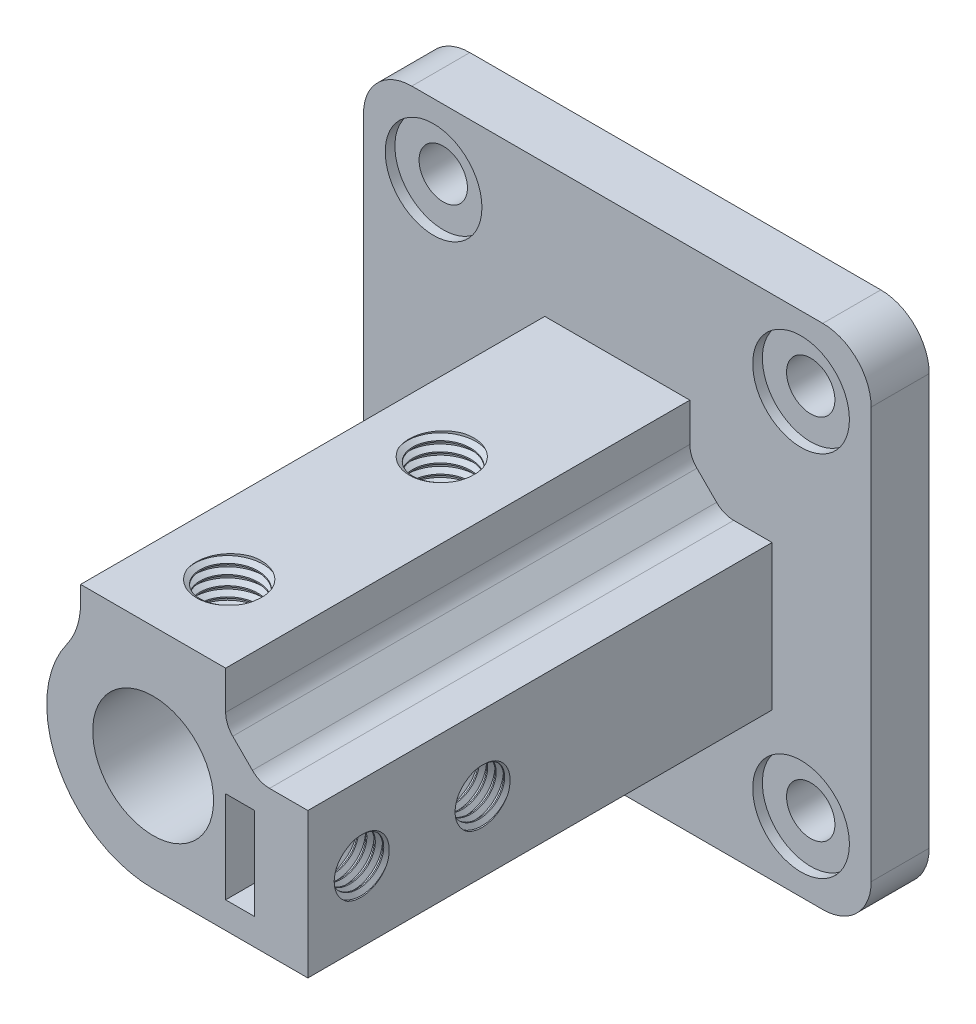
SolidWorks part; units mm, degrees
note: The reader was unsure of these and kept them because the rebuilt part matched: shared geometry of "Sketch1<4>", "Sketch1<5>".
ref_plane "Front Plane" through (0, 0, 0) normal (0, 0, 1) x (1, 0, 0)
ref_plane "Top Plane" through (0, 0, 0) normal (0, 1, 0) x (1, 0, 0)
ref_plane "Right Plane" through (0, 0, 0) normal (1, 0, 0) x (0, 0, -1)
sketch "Sketch1" plane through (0, 0, 0) normal (0, 0, 1) x (1, 0, 0)
  line L0 (0, 0) -> (-131291.8989, 0) construction
  line L1 (0, 0) -> (0, -131291.8989) construction
  line L2 (-15, 25) -> (15, 25)
  line L3 (0, -22) -> (32, -22)
  line L4 (-15, 25) -> (-15, 21.6564)
  line L5 (15, 25) -> (15, 17.0711)
  line L6 (32, -22) -> (32, 8)
  line L8 (24.0711, 8) -> (32, 8)
  line L9 (32, -7) -> (8.3062, -7) construction
  line L10 (-42.5, 52.5) -> (42.5, 52.5)
  line L11 (-52.5, 42.5) -> (-52.5, -42.5)
  line L12 (-42.5, -52.5) -> (42.5, -52.5)
  line L13 (52.5, 42.5) -> (52.5, -42.5)
  line L14 (0, -52.5) -> (0, 52.5) construction
  line L15 (-52.5, 0) -> (52.5, 0) construction
  line L16 (20.5355, 9.4645) -> (16.4645, 13.5355)
  line L17 (15, 2.5) -> (21, 2.5)
  line L18 (15, 2.5) -> (15, -16.5)
  line L19 (15, -16.5) -> (21, -16.5)
  line L20 (21, 2.5) -> (21, -16.5)
  line L21 (18, -16.5) -> (18, 2.5) construction
  line L22 (15, -7) -> (21, -7) construction
  arc A0 (-17.8378, 12.8768) -> (0, -22) centre (0, 0) ccw
  arc A2 (-17.8378, 12.8768) -> (-15, 21.6564) centre (-30, 21.6564) ccw
  arc A3 (-52.5, -42.5) -> (-42.5, -52.5) centre (-42.5, -42.5) ccw
  arc A4 (42.5, -52.5) -> (52.5, -42.5) centre (42.5, -42.5) ccw
  arc A5 (42.5, 52.5) -> (52.5, 42.5) centre (42.5, 42.5) cw
  arc A6 (-42.5, 52.5) -> (-52.5, 42.5) centre (-42.5, 42.5) ccw
  arc A7 (20.5355, 9.4645) -> (24.0711, 8) centre (24.0711, 13) ccw
  arc A8 (16.4645, 13.5355) -> (15, 17.0711) centre (20, 17.0711) cw
  point P10 (0, 25)
  point P21 (-52.5, -52.5)
  point P24 (52.5, -52.5)
  point P34 (18, -7)
  point P41 (22, 8)
  dimension "D1" = 44
  dimension "D6" = 15
  dimension "D8" = 10
  dimension "D14" = 5
  dimension "D2" = 30
  dimension "D3" = 30
  dimension "D4" = 25
  dimension "D5" = 32
  dimension "D7" = 105
  dimension "D9" = 19
  dimension "D10" = 6
  dimension "D11" = 11
  dimension "D12" = 135
  dimension "D13" = 10
extrude "Boss-Extrude1" add sketch "Sketch1" along normal blind 12 contours L10 A6 L11 A3 L12 A4 L13 A5 A0 A2 L4 L2 L5 L8 L6 L3 | A2 A0 L3 L6 L8 L5 L2 L4 L17 L20 L19 L18 | L20 L17 L18 L19
extrude "Boss-Extrude2" add sketch "Sketch1<4>" along normal blind 108 contours A0 L3 L6 L8 A7 L16 A8 L5 L2 L4 A2
sketch "Sketch1<4>" plane through (0, 0, 0) normal (0, 0, 1) x (1, 0, 0) same geometry as "Sketch1"
extrude "Cut-Extrude1" cut sketch "Sketch1<5>" against normal blind 48 from surface at 108 contours L20 L19 L18 L17 starting at face at (8.7964, 8.2207, 108)
sketch "Sketch1<5>" plane through (0, 0, 0) normal (0, 0, 1) x (1, 0, 0) same geometry as "Sketch1"
hole_wizard "Ø25.0mm Dowel Hole1" positions "3DSketch1" profile "Sketch2" hole size "Ø25.0" standard "ANSI Metric"
sketch3d "3DSketch1"
  line L0 (0, 0, 108) -> (0, 0, 12) construction
  point P0 (0, 0, 108)
sketch "Sketch2" plane through (0, 0, 108) normal (1, 0, 0) x (0, -1, 0)
  line L0 (0, 0) -> (0, 82)
  line L1 (0, 82) -> (12.5, 74.4892)
  line L2 (12.5, 74.4892) -> (12.5, 0)
  line L5 (12.5, 0) -> (0, 0)
  line L10 (0, 82) -> (-12.5, 74.4892) construction
  line L11 (0, -6.35) -> (0, 107.95) construction
  dimension "Hole Dia." = 25
  dimension "Hole Depth" = 82
  dimension "Drill Angle" = 118
hole_wizard "CBORE for M5 Hex Head Bolt1" positions "3DSketch3" profile "Sketch4" counterbore size "M5" standard "ANSI Metric" end condition through all
sketch3d "3DSketch3"
  line L0 (-52.5, 42.5, 12) -> (-52.5, -42.5, 12) construction
  line L1 (-42.5, 52.5, 12) -> (42.5, 52.5, 12) construction
  point P0 (38, 38.0257, 12)
  point P2 (-38, 38, 12)
  dimension "D1" = 76
  dimension "D2" = 14.5
  dimension "D3" = 14.5
sketch "Sketch4" plane through (38, 38.0257, 12) normal (1, 0, 0) x (0, -1, 0)
  line L0 (0, 0) -> (0, 12)
  line L1 (0, 12) -> (5, 12)
  line L3 (5, 12) -> (5, 2)
  line L4 (5, 2) -> (10, 2)
  line L5 (10, 2) -> (10, 0)
  line L7 (10, 0) -> (0, 0)
  line L11 (0, -6.35) -> (0, 107.95) construction
  dimension "Thru Hole Dia." = 10
  dimension "Thru Hole Depth" = 12
  dimension "C'Bore Dia." = 20
  dimension "C'Bore Depth" = 2
mirror "Mirror1" about plane through (0, 0, 0) normal (0, 1, 0) of "CBORE for M5 Hex Head Bolt1"
hole_wizard "M12x1.75 Tapped Hole1" positions "3DSketch6" profile "Sketch6" tap size "M12x1.75" standard "ANSI Metric"
sketch3d "3DSketch6"
  line L0 (32, -22, 108) -> (32, -22, 12) construction
  line L1 (32, -22, 108) -> (32, 8, 108) construction
  point P0 (32, -7, 97)
  point P2 (32, -7, 72)
  point P5 (0, 0, 0)
  dimension "D1" = 25
  dimension "D2" = 15
  dimension "D3" = 11
sketch "Sketch6" plane through (32, -7, 97) normal (0, 1, 0) x (0, 0, -1)
  line L0 (0, 0) -> (0, 14.0644)
  line L1 (0, 14.0644) -> (5.1, 11)
  line L2 (5.1, 11) -> (5.1, 0)
  line L5 (5.1, 0) -> (0, 0)
  line L10 (0, 14.0644) -> (-5.1, 11) construction
  line L11 (0, -6.35) -> (0, 107.95) construction
  dimension "Tap Drill Dia." = 10.2
  dimension "Tap Drill Depth" = 11
  dimension "Drill Angle" = 118
cosmetic thread "Hole Thread1" parameters "D1"=24, "D2"=12
cosmetic thread "Hole Thread2" parameters "D1"=24, "D2"=12
thread "Thread1" pitch 1.75 start angle 0, offset 2, length 15, pitch 1.75, diameter 10.2
ref_plane "Plane1" through (34, -7, 77.1) normal (0, 1, 0) x (0, 0, -1)
sketch "Thread Profile1" plane through (34, -7, 77.1) normal (0, 1, 0) x (0, 0, -1)
  line L0 (0, 0) -> (0, 1.75) construction
  line L11 (0, 0) -> (0, 1.5312)
  line L12 (0, 1.5312) -> (-0.9472, 0.9844)
  line L13 (-0.9472, 0.9844) -> (-0.9472, 0.5469)
  line L15 (-0.9472, 0.5469) -> (0, 0)
  line L17 (-0.9472, 0.7656) -> (0, 0.7656) construction
  point P2 (0, 0)
  dimension "Pitch" = 1.75
  dimension "Profile_Angle" = 60
  dimension "Profile_Land" = 0.4375
  dimension "Profile_Height" = 0.9472
thread "Thread2" pitch 1.75 profile "Thread Profile2" start angle 0, offset 2, length 15, pitch 1.75, diameter 10.2
ref_plane "Plane2" through (34, -7, 102.1) normal (0, 1, 0) x (0, 0, -1)
sketch "Thread Profile2" plane through (34, -7, 102.1) normal (0, 1, 0) x (0, 0, -1)
  line L0 (0, 0) -> (0, 1.75) construction
  line L11 (0, 0) -> (0, 1.5312)
  line L12 (0, 1.5312) -> (-0.9472, 0.9844)
  line L13 (-0.9472, 0.9844) -> (-0.9472, 0.5469)
  line L15 (-0.9472, 0.5469) -> (0, 0)
  line L17 (-0.9472, 0.7656) -> (0, 0.7656) construction
  point P2 (0, 0)
  dimension "Pitch" = 1.75
  dimension "Profile_Angle" = 60
  dimension "Profile_Land" = 0.4375
  dimension "Profile_Height" = 0.9472
hole_wizard "M14x2.0 Tapped Hole1" positions "3DSketch7" profile "Sketch11" tap size "M14x2.0" standard "ANSI Metric"
sketch3d "3DSketch7"
  line L0 (-15, 25, 108) -> (15, 25, 108) construction
  line L1 (-15, 25, 108) -> (-15, 25, 12) construction
  point P0 (0, 25, 92)
  point P2 (0, 25, 48)
  point P7 (0, 0, 0)
  dimension "D1" = 44
  dimension "D2" = 16
  dimension "D3" = 15
sketch "Sketch11" plane through (0, 25, 92) normal (1, 0, 0) x (0, 0, 1)
  line L0 (0, 0) -> (0, 12.5)
  line L1 (0, 12.5) -> (6, 12.5)
  line L2 (6, 12.5) -> (6, 0)
  line L5 (6, 0) -> (0, 0)
  line L11 (0, -6.35) -> (0, 107.95) construction
  dimension "Thru Tap Drill Dia." = 12
  dimension "Thru Tap Drill Depth" = 12.5
cosmetic thread "Hole Thread3" parameters "D2"=14
cosmetic thread "Hole Thread4" parameters "D2"=14
thread "Thread3" pitch 2 profile "Thread Profile3" start angle 0, offset 3, length 20, pitch 2, diameter 12
ref_plane "Plane3" through (-6, 28, 48) normal (0, 0, -1) x (1, 0, 0)
sketch "Thread Profile3" plane through (-6, 28, 48) normal (0, 0, -1) x (1, 0, 0)
  line L0 (0, 0) -> (0, 2) construction
  line L11 (0, 0) -> (0, 1.75)
  line L12 (0, 1.75) -> (-1.0825, 1.125)
  line L13 (-1.0825, 1.125) -> (-1.0825, 0.625)
  line L15 (-1.0825, 0.625) -> (0, 0)
  line L17 (-1.0825, 0.875) -> (0, 0.875) construction
  point P2 (0, 0)
  dimension "Pitch" = 2
  dimension "Profile_Angle" = 60
  dimension "Profile_Land" = 0.5
  dimension "Profile_Height" = 1.0825
thread "Thread4" pitch 2 profile "Thread Profile4" start angle 3, offset 3, length 20, pitch 2, diameter 12
ref_plane "Plane4" through (-5.9918, 28, 91.686) normal (0.0523, 0, -0.9986) x (0.9986, 0, 0.0523)
sketch "Thread Profile4" plane through (-5.9918, 28, 91.686) normal (0.0523, 0, -0.9986) x (0.9986, 0, 0.0523)
  line L0 (0, 0) -> (0, 2) construction
  line L11 (0, 0) -> (0, 1.75)
  line L12 (0, 1.75) -> (-1.0825, 1.125)
  line L13 (-1.0825, 1.125) -> (-1.0825, 0.625)
  line L15 (-1.0825, 0.625) -> (0, 0)
  line L17 (-1.0825, 0.875) -> (0, 0.875) construction
  point P2 (0, 0)
  dimension "Pitch" = 2
  dimension "Profile_Angle" = 60
  dimension "Profile_Land" = 0.5
  dimension "Profile_Height" = 1.0825
